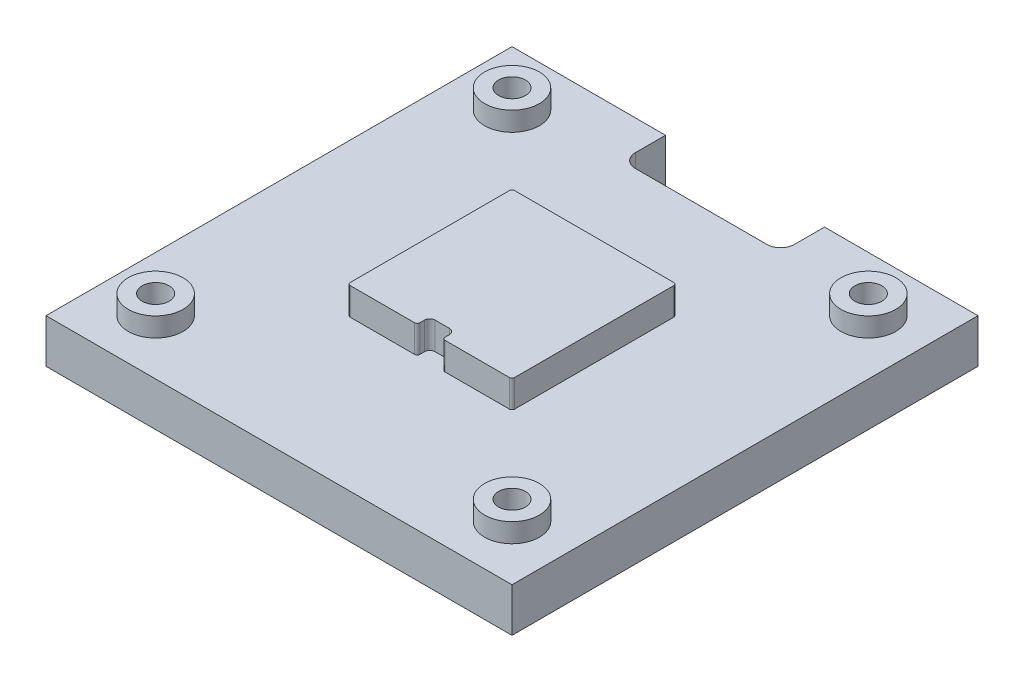
SolidWorks part; units mm, degrees
material "Copper"
ref_plane "Front Plane" through (0, 0, 0) normal (0, 0, 1) x (1, 0, 0)
ref_plane "Top Plane" through (0, 0, 0) normal (0, 1, 0) x (1, 0, 0)
ref_plane "Right Plane" through (0, 0, 0) normal (1, 0, 0) x (0, 0, -1)
sketch "Sketch1" plane through (0, 0, 0) normal (0, 1, 0) x (1, 0, 0)
  line L0 (-55, 0) -> (55, 0) construction
  line L1 (-42.5, 42.5) -> (42.5, 42.5)
  line L2 (-42.5, 42.5) -> (-42.5, -42.5)
  line L3 (-42.5, -42.5) -> (42.5, -42.5)
  line L4 (42.5, 42.5) -> (42.5, -42.5)
  line L5 (-42.5, 42.5) -> (42.5, -42.5) construction
  line L6 (-42.5, -42.5) -> (42.5, 42.5) construction
  line L7 (0, -55) -> (0, 55) construction
  circle A0 centre (-32.5, 32.5) radius 2.4575
  circle A1 centre (-32.5, -32.5) radius 2.4575
  circle A2 centre (32.5, -32.5) radius 2.4575
  circle A3 centre (32.5, 32.5) radius 2.4575
  point P0 (0, 0)
  dimension "D3" = 4.915
  dimension "D1" = 85
  dimension "D2" = 85
  dimension "D4" = 65
  dimension "D5" = 65
extrude "Boss-Extrude1" add sketch "Sketch1" along normal blind 8
sketch "Sketch2" plane through (0, 0, 0) normal (0, -1, 0) x (1, 0, 0)
  line L0 (0, -55) -> (0, 55) construction
  line L1 (55, 0) -> (-55, 0) construction
  circle A0 centre (-32.5, 32.5) radius 3.969
  circle A1 centre (32.5, 32.5) radius 3.969
  circle A2 centre (32.5, -32.5) radius 3.969
  circle A3 centre (-32.5, -32.5) radius 3.969
  dimension "D1" = 7.938
extrude "Cut-Extrude1" cut sketch "Sketch2" against normal blind 4.166
sketch "Sketch3" plane through (0, 8, 0) normal (0, 1, 0) x (1, 0, 0)
  line L0 (0, -55) -> (0, 55) construction
  line L1 (-55, 0) -> (55, 0) construction
  circle A0 centre (32.5, -32.5) radius 5
  circle A1 centre (32.5, -32.5) radius 2.4575
  circle A2 centre (32.5, -32.5) radius 2.4575 construction
  circle A3 centre (-32.5, -32.5) radius 2.4575
  circle A4 centre (-32.5, -32.5) radius 5
  circle A5 centre (-32.5, 32.5) radius 5
  circle A6 centre (-32.5, 32.5) radius 2.4575
  circle A7 centre (32.5, 32.5) radius 2.4575
  circle A8 centre (32.5, 32.5) radius 5
  dimension "D1" = 10
extrude "Boss-Extrude2" add sketch "Sketch3" along normal blind 3.5
sketch "Sketch4" plane through (0, 8, 0) normal (0, 1, 0) x (1, 0, 0)
  line L0 (2.2929, -14.5) -> (2.2929, -13.7071)
  line L1 (14.5, -15) -> (2.7929, -15)
  line L2 (15, -14.5) -> (15, 14.5)
  line L3 (14.5, 15) -> (-14.5, 15)
  line L4 (-15, -14.5) -> (-15, 14.5)
  line L5 (15, -15) -> (-15, 15) construction
  line L6 (15, 15) -> (-15, -15) construction
  line L7 (1.2929, -12.7071) -> (-1.2929, -12.7071)
  line L8 (-2.2929, -13.7071) -> (-2.2929, -14.5)
  line L9 (-2.7929, -15) -> (-14.5, -15)
  arc A0 (-14.5, 15) -> (-15, 14.5) centre (-14.5, 14.5) ccw
  arc A1 (15, 14.5) -> (14.5, 15) centre (14.5, 14.5) ccw
  arc A2 (-14.5, -15) -> (-15, -14.5) centre (-14.5, -14.5) cw
  arc A3 (14.5, -15) -> (15, -14.5) centre (14.5, -14.5) ccw
  arc A4 (-2.2929, -14.5) -> (-2.7929, -15) centre (-2.7929, -14.5) cw
  arc A5 (2.2929, -14.5) -> (2.7929, -15) centre (2.7929, -14.5) ccw
  arc A6 (-1.2929, -12.7071) -> (-2.2929, -13.7071) centre (-1.2929, -13.7071) ccw
  arc A7 (2.2929, -13.7071) -> (1.2929, -12.7071) centre (1.2929, -13.7071) ccw
  point P0 (0, 0)
  point P10 (0, -12.7071)
  point P25 (-2.2929, -15)
  point P30 (-2.2929, -12.7071)
  point P33 (2.2929, -12.7071)
  dimension "D4" = 0.5
  dimension "D6" = 0.5
  dimension "D7" = 1
  dimension "D1" = 30
  dimension "D2" = 2.2929
  dimension "D3" = 4.5858
  dimension "D5" = 30
extrude "Boss-Extrude3" add sketch "Sketch4" along normal blind 5
sketch "Sketch5" plane through (0, 8, 0) normal (0, 1, 0) x (1, 0, 0)
  line L0 (42.5, 42.5) -> (-42.5, 42.5) construction
  line L1 (14.5, 42.5) -> (-14.5, 42.5)
  line L2 (14.5, 42.5) -> (14.5, 34.5)
  line L3 (14.5, 34.5) -> (-14.5, 34.5)
  line L4 (-14.5, 42.5) -> (-14.5, 34.5)
  point P6 (0, 34.5)
  dimension "D1" = 29
  dimension "D2" = 8
extrude "Cut-Extrude2" cut sketch "Sketch5" against normal blind 10
fillet "Fillet1" radius 2.5 2 edges at (-14.5, 4, -34.5) (14.5, 4, -34.5)
